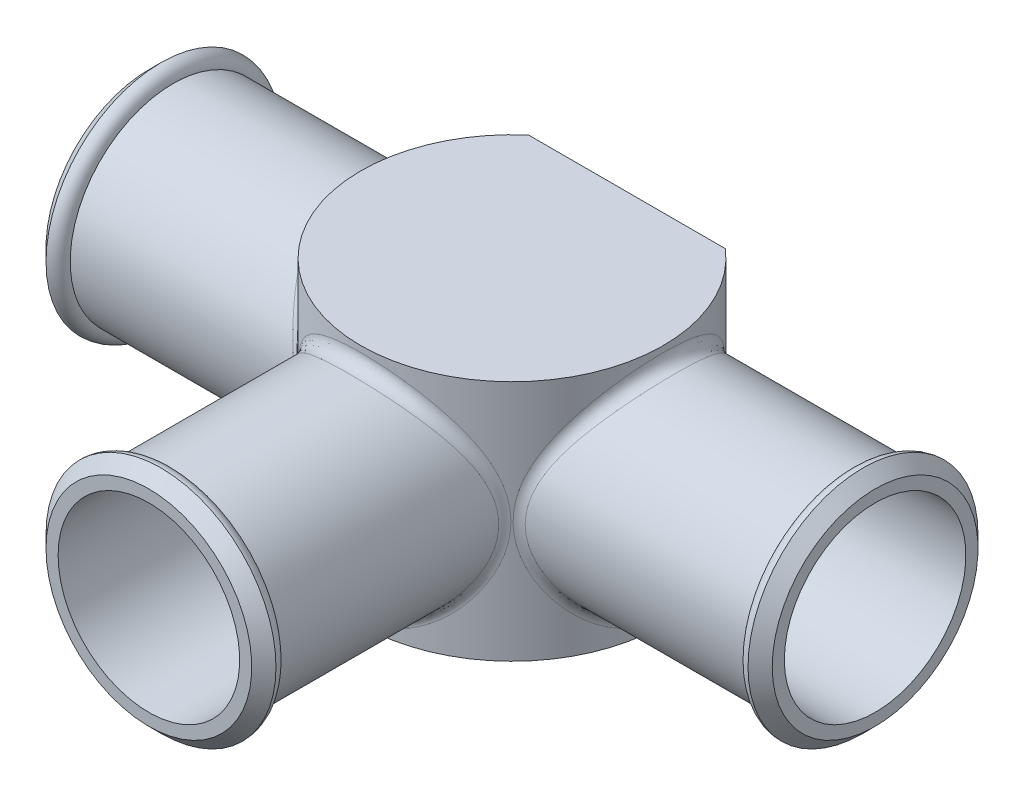
SolidWorks part; units mm, degrees
ref_plane "X-Y Datum" through (0, 0, 0) normal (0, 0, 1) x (1, 0, 0)
ref_plane "X-Z Datum" through (0, 0, 0) normal (0, 1, 0) x (1, 0, 0)
ref_plane "Y-Z Datum" through (0, 0, 0) normal (1, 0, 0) x (0, 0, -1)
sketch "Sketch1" plane through (0, 0, 0) normal (0, 1, 0) x (1, 0, 0)
  line L0 (-10.3175, 12.065) -> (10.3175, 12.065)
  line L1 (-36.6593, 15.875) -> (32.8085, 15.875) construction
  circle A0 centre (0, 0) radius 15.875
  dimension "D1" = 31.75
  dimension "D2" = 3.81
extrude "Boss-Extrude1" add sketch "Sketch1" along normal blind 25.4 contours L0 A0 region at (0, 0, 0.9923)
sketch "Sketch3" plane through (0, 0, 0) normal (0, 0, 1) x (1, 0, 0)
  line L0 (-15.875, 0) -> (15.875, 0) construction
  line L4 (15.875, 25.4) -> (-15.875, 25.4) construction
  line L5 (15.875, 0) -> (15.875, 25.4) construction
  line L6 (-15.875, 0) -> (15.875, 0) construction
  line L7 (15.875, 25.4) -> (-15.875, 25.4) construction
  line L8 (15.875, 0) -> (15.875, 25.4) construction
  line L9 (0, 25.4) -> (0, 0) construction
  line L10 (0, 12.7) -> (41.275, 12.7)
  dimension "D1" = 25.4
sweep "Cut-Sweep1" cut path "Sketch3" circular profile diameter 19.05 parameters "D3"=19.05
sketch "Sketch10" plane through (0, 0, 0) normal (0, 0, 1) x (1, 0, 0)
  line L0 (-15.875, 0) -> (15.875, 0) construction
  line L1 (15.875, 25.4) -> (-15.875, 25.4) construction
  line L2 (-15.875, 0) -> (15.875, 0) construction
  line L3 (15.875, 25.4) -> (-15.875, 25.4) construction
  line L4 (0, 0) -> (0, 25.4) construction
  line L5 (0, 12.7) -> (25.4, 12.7) construction
  line L6 (0, 22.225) -> (38.1, 22.225)
  line L7 (38.1, 22.225) -> (38.1, 24.765)
  line L8 (38.1, 24.765) -> (35.56, 24.765)
  line L9 (35.56, 24.765) -> (35.56, 23.495)
  line L10 (35.56, 23.495) -> (0, 23.495)
  line L11 (0, 23.495) -> (0, 22.225)
  dimension "D1" = 25.4
  dimension "D2" = 1.27
  dimension "D3" = 1.27
  dimension "D4" = 2.54
  dimension "D5" = 38.1
  dimension "D6" = 9.525
revolve "Revolve1" add sketch "Sketch10" angle 360 about L5
pattern_circular "CirPattern1" count 3 over 180 about axis through (0, 25.4, 0) along (0, -1, 0) of "Revolve1", "Cut-Sweep1"
sketch "Sketch20" plane through (0, 0, 0) normal (1, 0, 0) x (0, 0, -1)
  line L1 (0, 3.175) -> (0, 22.225)
  line L2 (0, 3.175) -> (0, 22.225)
  arc A1 (0, 22.225) -> (0, 3.175) centre (0, 12.7) ccw
  arc A2 (0, 22.225) -> (0, 3.175) centre (0, 12.7) ccw
  dimension "D1" = 0
extrude "Cut-Extrude2" cut sketch "Sketch20" against normal through all both and the other way through all
sketch "Sketch23" plane through (0, 0, 0) normal (0, 0, 1) x (1, 0, 0)
  line L1 (0, 3.175) -> (0, 22.225)
  line L2 (0, 3.175) -> (0, 22.225)
  arc A1 (0, 22.225) -> (0, 3.175) centre (0, 12.7) ccw
  arc A2 (0, 22.225) -> (0, 3.175) centre (0, 12.7) ccw
  dimension "D1" = 0
extrude "Cut-Extrude3" cut sketch "Sketch23" along normal through all
chamfer "Chamfer1" distance 1.27 angle 45 3 edges at (-38.1, 12.7, -12.065) (-12.065, 12.7, 38.1) (38.1, 12.7, 12.065)
fillet "Fillet1" radius 1.27 6 edges at (-11.7469, 14.2829, 10.6783) (11.7469, 14.2829, -10.6783) (10.6783, 14.2829, 11.7469) (-12.065, 12.7, 35.56) (35.56, 12.7, 12.065) (-35.56, 12.7, -12.065)
